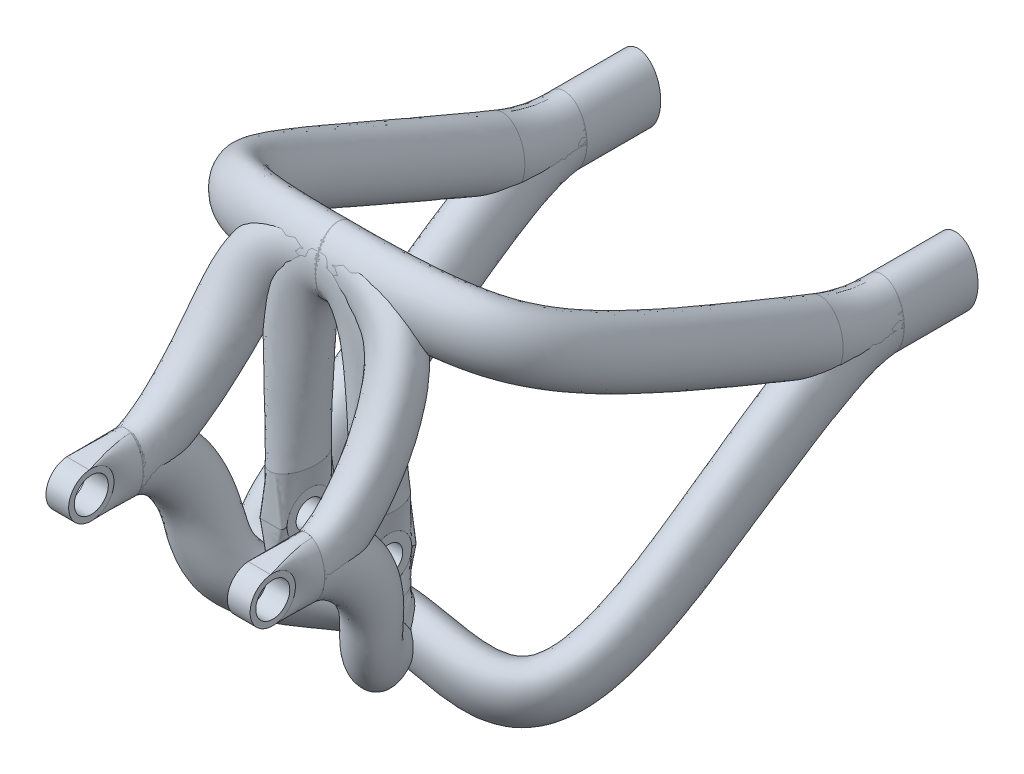
SolidWorks part; units mm, degrees
ref_plane "Płaszczyzna przednia" through (0, 0, 0) normal (0, 0, 1) x (1, 0, 0)
ref_plane "Płaszczyzna górna" through (0, 0, 0) normal (0, 1, 0) x (1, 0, 0)
ref_plane "Płaszczyzna prawa" through (0, 0, 0) normal (1, 0, 0) x (0, 0, -1)
sketch "Baza - płaszczyzna górna" plane through (0, 0, 0) normal (0, 1, 0) x (1, 0, 0)
  line L0 (0, 0) -> (0, 512) construction
  line L1 (117.5, 147.6) -> (-117.5, 147.6) construction
  line L2 (135, 0) -> (-135, 0) construction
  line L3 (-117.5, 512) -> (117.5, 512) construction
  line L4 (-117.5, 512) -> (-117.5, 147.6) construction
  line L5 (117.5, 512) -> (117.5, 147.6) construction
  line L6 (117.5, 186) -> (-117.5, 186) construction
  line L7 (135, 22.5) -> (135, -22.5) construction
  line L8 (-135, 22.5) -> (-135, -22.5) construction
  line L9 (117.5, 512) -> (125, 512) construction
  line L10 (125, 512) -> (125, 147.6) construction
  line L11 (125, 147.6) -> (117.5, 147.6) construction
  point P2 (0, 487)
  point P7 (0, 0)
  point P10 (0, 512)
  point P12 (0, 147.6)
  point P16 (135, 0)
  dimension "D1" = 512
  dimension "D2" = 147.6
  dimension "D3" = 270
  dimension "D4" = 235
  dimension "D5" = 326
  dimension "D6" = 45
  dimension "D7" = 25
  dimension "D8" = 125
sketch "Baza - płaszczyzna prawa" plane through (0, 0, 0) normal (1, 0, 0) x (0, 0, -1)
  line L0 (0, 0) -> (512, 0) construction
  line L1 (0, 0) -> (512, 0) construction
  line L2 (147.6, 0) -> (147.6, -66) construction
  arc A2 (440.6668, 297.4126) -> (440.6668, -297.4126) centre (487, 0) ccw
  dimension "D5" = 301
  dimension "D1" = 66
  dimension "D2" = 147.6
ref_plane "Powierzchnia styku z ramą" through (135, 0, 0) normal (1, 0, 0) x (0, 0, -1)
sketch "Szkic - insert - rama" plane through (135, 0, 0) normal (1, 0, 0) x (0, 0, -1)
  circle A0 centre (0, 0) radius 20
  circle A1 centre (0, 0) radius 15
  dimension "D1" = 40
  dimension "D2" = 30
ref_plane "Powierzchnia graniczna koła" through (125, 0, 0) normal (1, 0, 0) x (0, 0, -1)
ref_plane "Płaszczyzna pracy łańcucha" through (100, 0, 0) normal (1, 0, 0) x (0, 0, -1)
sketch "Łańcuch - baza" plane through (100, 0, 0) normal (1, 0, 0) x (0, 0, -1)
  line L0 (0, 0) -> (-72.4444, -19.4114) construction
  line L1 (0, 0) -> (512, 0) construction
  dimension "D1" = 75
  dimension "D2" = 165
sketch "Łańcuch - zarys" plane through (100, 0, 0) normal (1, 0, 0) x (0, 0, -1)
  line L0 (-75.0521, 2.4335) -> (503.4658, 71.4924)
  line L1 (-83.5151, 37.5222) -> (483.2736, 147.733)
  line L2 (-72.4444, -19.4114) -> (512, 0) construction
  line L3 (-79.7129, -76.9542) -> (493.1396, -149.3135)
  line L4 (-73.5969, -41.3812) -> (508.2284, -71.9011)
  circle A0 centre (-72.4444, -19.4114) radius 22
  circle A1 centre (512, 0) radius 72
  arc A2 (-83.5151, 37.5222) -> (-79.7129, -76.9542) centre (-72.4444, -19.4114) ccw
  arc A3 (493.1396, -149.3135) -> (483.2736, 147.733) centre (512, 0) ccw
  point P0 (-72.4444, -19.4114)
  point P2 (512, 0)
  dimension "D1" = 44
  dimension "D2" = 144
  dimension "D3" = 116
  dimension "D4" = 301
ref_axis "Oś tynego koła" through (-117.5, 0, -512) along (1, 0, 0)
ref_axis "Oś mocowania do ramy" through (135, 0, 0) along (-1, 0, 0)
ref_axis "Oś mocowania linkage" through (0, -66, -147.6) along (1, 0, 0)
sketch "Szkic - insert - linkage" plane through (0, 0, 0) normal (1, 0, 0) x (0, 0, -1)
  circle A0 centre (147.6, -66) radius 12
  circle A1 centre (147.6, -66) radius 20
  dimension "D1" = 40
  dimension "D2" = 24
extrude "Rama" add sketch "Szkic - insert - rama" against normal mid plane 20 from offset 55 offset against normal yes
extrude "Linkage" add sketch "Szkic - insert - linkage" along normal blind 20 from offset 25 separate body
sketch "Szkic - insert - tylne koło" plane through (125, 0, 0) normal (1, 0, 0) x (0, 0, -1)
  line L0 (487, 20) -> (552, 20)
  line L1 (512, 0) -> (147.6, 0) construction
  line L2 (487, -20) -> (552, -20)
  line L3 (537, 8) -> (487, 8)
  line L4 (537, -8) -> (487, -8)
  line L5 (552, -20) -> (552, 20)
  arc A1 (487, 8) -> (487, -8) centre (487, 0) ccw
  arc A2 (537, -8) -> (537, 8) centre (537, 0) ccw
  arc A3 (487, 20) -> (487, -20) centre (487, 0) ccw
  dimension "D1" = 40
  dimension "D3" = 8
  dimension "D2" = 65
  dimension "D4" = 487
  dimension "D5" = 537
extrude "Tylne koło" add sketch "Szkic - insert - tylne koło" along normal blind 15 separate body
sketch "Szkic otwór łańcuch" plane through (0, 0, 0) normal (0, 0, 1) x (1, 0, 0)
  line L3 (100, -130) -> (110, -130)
  line L13 (115, -125) -> (115, -45)
  line L14 (110, -40) -> (100, -40)
  line L15 (95, -45) -> (95, -125)
  arc A0 (100, -130) -> (95, -125) centre (100, -125) cw
  arc A1 (110, -130) -> (115, -125) centre (110, -125) ccw
  arc A2 (115, -45) -> (110, -40) centre (110, -45) ccw
  arc A3 (100, -40) -> (95, -45) centre (100, -45) ccw
  dimension "D1" = 5
  dimension "D2" = 95
  dimension "D3" = 20
  dimension "D4" = 40
  dimension "D5" = 90
ref_plane "Płaszczyzna1" through (0, 0, -552) normal (0, 0, 1) x (1, 0, 0)
sketch "Szkic1" plane through (0, 0, -552) normal (0, 0, 1) x (1, 0, 0)
  line L0 (125, -20) -> (125, 20) construction
  line L1 (125, -20) -> (125, 20) construction
  ellipse E0 centre (139.9071, 0) end of major axis (139.9071, -30) minor radius 20
  dimension "D1" = 40
  dimension "D2" = 60
ref_plane "Płaszczyzna2" through (0, 0, -487) normal (0, 0, 1) x (1, 0, 0)
sketch "Szkic2" plane through (0, 0, -487) normal (0, 0, 1) x (1, 0, 0)
  ellipse E0 centre (139.9071, 0) end of major axis (139.9071, -30) minor radius 20 construction
  ellipse E1 centre (139.9071, 0) end of major axis (139.9071, -30) minor radius 20
sketch3d "Szkic 3D1"
  line L0 (139.9071, 0, -487) -> (139.9071, 0, -552)
  line L2 (0, 0, -147.6) -> (0, 158.7201, -147.6) construction
  line L3 (119.3246, 140, -147.6) -> (-119.3246, 140, -147.6) construction
  line L4 (140.0724, 7.5182, -440.5114) -> (140.5573, 28.6822, -388.43) construction
  line L5 (139.9071, 0, -502.2142) -> (139.9071, 0, -471.7253) construction
  spline S0 degree 3 poles (0, 140, -147.6) (156.552, 140, -147.6) (142.3562, 107.1992, -195.2116) (140.1456, 10.7124, -432.651) knots 0 0 0 0 0.922837 0.922837 0.922837 0.922837
  spline S1 degree 3 poles (140.1456, 10.7124, -432.651) (139.9436, 1.8941, -454.3516) (139.9071, 0, -467.9444) (139.9071, 0, -487) knots 0.922837 0.922837 0.922837 0.922837 1 1 1 1
  dimension "D1" = 140
surface "Powierzchnia-Wyciągnięcie po ścieżce2"
sketch3d "Szkic 3D2"
  circle A0 centre (70, 0, 0) radius 20 construction
  circle A1 centre (90, 0, 0) radius 20 construction
  arc A2 (70, -19.9375, -1.5799) -> (70, 19.9231, 1.7525) centre (70, 0, 0) ccw
  arc A3 (90, -19.9465, -1.4615) -> (90, 19.9268, 1.7094) centre (90, 0, 0) ccw
  circle A4 centre (70, 0, 0) radius 20 construction
  circle A5 centre (90, 0, 0) radius 20 construction
  circle A6 centre (70, 0, 0) radius 20 construction
  circle A7 centre (90, 0, 0) radius 20 construction
  spline S0 degree 1 poles (70, 19.9231, 1.7525) (90, 19.9268, 1.7094) knots 0 0 1 1
  spline S1 degree 1 poles (70, -19.9375, -1.5799) (90, -19.9465, -1.4615) knots 0 0 1 1
  point P2 (90, 0, 0)
  point P5 (110, 0, 0)
  point P7 (90, 0, 0)
  point P9 (110, 0, 0)
  point P14 (90, 0, 0)
  point P17 (110, 0, 0)
  point P22 (90, 0, 0)
  point P25 (110, 0, 0)
ref_plane "Płaszczyzna3" through (0, 0, -40) normal (0, 0, 1) x (1, 0, 0)
sketch "Szkic3" plane through (0, 0, -40) normal (0, 0, 1) x (1, 0, 0)
  line L0 (70, -19.9375) -> (70, 20) construction
  line L1 (90, -19.9465) -> (90, 20) construction
  line L2 (70, -19.9375) -> (70, 20) construction
  line L3 (90, -19.9465) -> (90, 20) construction
  line L4 (90, -19.9465) -> (70, 19.9231) construction
  line L5 (70, -19.9375) -> (90, 19.9268) construction
  ellipse E0 centre (80, -0.0117) end of major axis (80, 25.8035) minor radius 15.7433
  spline S0 degree 3 poles (-1929.9876, -19.0343) (-589.9986, -19.6394) (749.9903, -20.2446) (2089.9792, -20.8497) knots -99.999378 -99.999378 -99.999378 -99.999378 100.998962 100.998962 100.998962 100.998962 only from (70, -19.9375) to (90, -19.9465) construction
  spline S1 degree 3 poles (-1929.9879, 19.5485) (-589.9987, 19.7995) (749.9904, 20.0504) (2089.9796, 20.3013) knots -99.999395 -99.999395 -99.999395 -99.999395 100.998979 100.998979 100.998979 100.998979 only from (70, 19.9231) to (90, 19.9268) construction
  spline S2 degree 3 poles (70, -19.9375) (76.6667, -19.9405) (83.3333, -19.9435) (90, -19.9465) knots 0 0 0 0 1 1 1 1 construction
  spline S3 degree 3 poles (70, 19.9231) (76.6667, 19.9243) (83.3333, 19.9256) (90, 19.9268) knots 0 0 0 0 1 1 1 1 construction
  point P2 (80, -0.0117)
surface "Powierzchnia-Wyciągnięcie po profilach1" end constraint normal to profile end tangent length 1
sketch3d "Szkic 3D3"
  line L0 (0, 110, -147.6) -> (0, 170, -147.6) construction
  line L1 (0, 140, -147.6) -> (0, 140, -167.6) construction
  line L2 (0, 140, -167.6) -> (0, 140, -127.6) construction
  spline S0 degree 3 poles (0, 110, -147.6) (0, 110, -107.6) (0, 170, -107.6) (0, 170, -147.6) (0, 170, -187.6) (0, 110, -187.6) (0, 110, -147.6) (0, 110, -107.6) (0, 170, -107.6) knots -0.5 0 0 0 0.5 0.5 0.5 1 1 1 1.5 1.5 1.5 weights 1 0.333333 0.333333 1 0.333333 0.333333 1 0.333333 0.333333 only from (0, 110, -147.6) to (0, 110, -147.6) construction
  spline S1 degree 3 poles (0, 110, -147.6) (0, 110, -107.6) (0, 170, -107.6) (0, 170, -147.6) (0, 170, -187.6) (0, 110, -187.6) (0, 110, -147.6) (0, 110, -107.6) (0, 170, -107.6) knots -0.5 0 0 0 0.5 0.5 0.5 1 1 1 1.5 1.5 1.5 weights 1 0.333333 0.333333 1 0.333333 0.333333 1 0.333333 0.333333 only from (0, 110, -147.6) to (0, 110, -147.6)
sketch3d "Szkic 3D4"
  line L0 (-17.1198, 140, -147.6) -> (35.4624, 140, -147.6) construction
  line L1 (80, -0.0117, -59.3206) -> (80, -0.0117, -20.3916) construction
  spline S0 degree 3 poles (80, -0.0117, -40) (80, -0.0117, -64.3306) (75.1674, 69.9941, -132.2808) (59.2924, 140, -147.6) (0, 140, -147.6) knots 0 0 0 0 0.462724 1 1 1 1
surface "Powierzchnia-Wyciągnięcie po profilach3"
sketch "Szkic3<4>" plane through (0, 0, -40) normal (0, 0, 1) x (1, 0, 0) same geometry as "Szkic3"
sketch "Szkic4" plane through (0, 0, 0) normal (1, 0, 0) x (0, 0, -1)
  line L0 (179.3553, 0) -> (179.3553, -173.0425) construction
  line L1 (0, 0) -> (512, 0) construction
  line L2 (147.6, -66) -> (179.3553, -137.0609) construction
  ellipse E0 centre (179.3553, -137.0609) end of major axis (191.595, -164.4505) minor radius 20
  dimension "D1" = 60
  dimension "D2" = 40
sketch3d "Szkic 3D5"
  line L0 (139.9071, 0, -531.3863) -> (139.9071, 0, -439.8518) construction
  line L1 (18.4345, -137.0609, -179.3553) -> (-25.1846, -137.0609, -179.3553) construction
  spline S0 degree 3 poles (0, -137.0609, -179.3553) (69.0829, -137.0609, -179.3553) (118.485, -183.6678, -172.5611) (141.5721, -114.7186, -307.0519) (139.9071, 0, -439.2631) (139.9071, 0, -487) knots 0 0 0 0 0.519742 0.619742 1 1 1 1
surface "Powierzchnia-Wyciągnięcie po profilach4"
sketch3d "Szkic 3D6"
  line L0 (0, -164.0837, -192.3511) -> (0, -109.7304, -166.9846) construction
  line L1 (0, -109.7304, -166.9846) -> (0, -136.907, -179.6678) construction
  line L2 (-23.1985, -136.907, -179.6678) -> (23.1985, -136.907, -179.6678) construction
  line L3 (80, -0.0117, -41.42) -> (80, -0.0117, -5.881) construction
  line L4 (0, -145.5132, -161.2273) -> (0, -136.907, -179.6678) construction
  line L5 (0, -136.907, -179.6678) -> (0, -128.5954, -197.4772) construction
  spline S0 degree 3 poles (0, -164.3404, -191.8618) (0, -163.8269, -192.8403) (0, -163.2578, -193.7805) (0, -162.2463, -195.0746) (0, -161.0864, -196.2514) (0, -153.2931, -202.5999) (0, -139.6894, -202.8229) (0, -112.8437, -189.9122) (0, -104.9038, -176.1447) (0, -115.1727, -156.5743) (0, -131.4497, -154.4531) (0, -158.2953, -167.3638) (0, -166.2299, -177.9451) (0, -165.5626, -187.7206) (0, -165.269, -189.3139) (0, -164.7884, -190.8634) (0, -164.3404, -191.8618) (0, -163.8269, -192.8403) (0, -163.2578, -193.7805) knots -0.025 -0.0125 0 0 0.0125 0.025 0.0375 0.05 0.25 0.25 0.5 0.5 0.75 0.75 0.95 0.9625 0.975 0.9875 1 1 1.0125 1.025 1.0375 only from (0, -164.0837, -192.3511) to (0, -164.0837, -192.3511) construction
  spline S1 degree 3 poles (0, -164.3404, -191.8618) (0, -163.8269, -192.8403) (0, -163.2578, -193.7805) (0, -162.2463, -195.0746) (0, -161.0864, -196.2514) (0, -153.2931, -202.5999) (0, -139.6894, -202.8229) (0, -112.8437, -189.9122) (0, -104.9038, -176.1447) (0, -115.1727, -156.5743) (0, -131.4497, -154.4531) (0, -158.2953, -167.3638) (0, -166.2299, -177.9451) (0, -165.5626, -187.7206) (0, -165.269, -189.3139) (0, -164.7884, -190.8634) (0, -164.3404, -191.8618) (0, -163.8269, -192.8403) (0, -163.2578, -193.7805) knots -0.025 -0.0125 0 0 0.0125 0.025 0.0375 0.05 0.25 0.25 0.5 0.5 0.75 0.75 0.95 0.9625 0.975 0.9875 1 1 1.0125 1.025 1.0375 only from (0, -164.0837, -192.3511) to (0, -164.0837, -192.3511)
  spline S2 degree 3 poles (80, -0.0117, -40) (80, -0.0117, -62.2654) (82.1415, -27.0836, -100.0728) (62.3511, -135.8151, -110.0435) (25.5109, -136.907, -179.6678) (0, -136.907, -179.6678) knots 0 0 0 0 0.446189 0.546189 1 1 1 1
surface "Powierzchnia-Wyciągnięcie po profilach5"
sketch "Szkic3<6>" plane through (0, 0, -40) normal (0, 0, 1) x (1, 0, 0) same geometry as "Szkic3"
sketch3d "Szkic 3D7"
  line L0 (45, -66, -170.6) -> (45, -66, -169.5089)
  line L1 (25, -66, -193.7452) -> (25, -66, -101.6536) construction
  line L2 (45, -66, -125.6911) -> (45, -66, -124.6)
  line L3 (43, -66, -172.6) -> (27, -66, -172.6)
  line L4 (25, -66, -170.6) -> (25, -66, -169.5089)
  line L5 (43, -66, -122.6) -> (27, -66, -122.6)
  line L6 (25, -66, -125.6911) -> (25, -66, -124.6)
  line L7 (43, -66, -172.6) -> (27, -66, -122.6) construction
  line L8 (43, -66, -122.6) -> (27, -66, -172.6) construction
  line L9 (45, -46, -147.6) -> (25, -46, -147.6) construction
  circle A0 centre (45, -66, -147.6) radius 20 construction
  circle A1 centre (25, -66, -147.6) radius 20 construction
  arc A2 (45, -64.1818, -167.5172) -> (45, -64.1818, -127.6828) centre (45, -66, -147.6) ccw
  arc A3 (25, -64.1818, -167.5172) -> (25, -64.1818, -127.6828) centre (25, -66, -147.6) ccw
  arc A4 (27, -66, -122.6) -> (25, -66, -124.6) centre (27, -66, -124.6) ccw
  arc A5 (43, -66, -122.6) -> (45, -66, -124.6) centre (43, -66, -124.6) ccw
  arc A6 (45, -66, -125.6911) -> (45, -64.1818, -127.6828) centre (45, -64, -125.6911) ccw
  arc A7 (25, -66, -125.6911) -> (25, -64.1818, -127.6828) centre (25, -64, -125.6911) ccw
  arc A8 (45, -64.1818, -167.5172) -> (45, -66, -169.5089) centre (45, -64, -169.5089) ccw
  arc A9 (45, -66, -170.6) -> (43, -66, -172.6) centre (43, -66, -170.6) ccw
  arc A10 (27, -66, -172.6) -> (25, -66, -170.6) centre (27, -66, -170.6) ccw
  arc A11 (25, -64.1818, -167.5172) -> (25, -66, -169.5089) centre (25, -64, -169.5089) ccw
  point P6 (65, -66, -147.6)
  point P9 (45, -66, -147.6)
  point P11 (65, -66, -147.6)
  point P13 (45, -66, -147.6)
  point P20 (25, -66, -122.6)
  point P21 (27, -68, -124.6)
  point P24 (45, -66, -122.6)
  point P25 (43, -64, -124.6)
  point P28 (47, -64, -125.6911)
  point P31 (27, -64, -125.6911)
  point P34 (47, -64, -169.5089)
  point P37 (45, -66, -172.6)
  point P38 (43, -64, -170.6)
  point P41 (25, -66, -172.6)
  point P42 (27, -64, -170.6)
  point P45 (27, -64, -169.5089)
  point P48 (35, -46, -147.6)
  dimension "D2" = 2
  dimension "D1" = 50
ref_plane "Płaszczyzna4" through (0, -66, 0) normal (0, 1, 0) x (1, 0, 0)
sketch3d "Szkic 3D8"
  line L0 (43, -66, -172.6) -> (27, -66, -172.6) construction
  line L1 (45, -66, -170.6) -> (45, -66, -169.5089) construction
  line L2 (25, -66, -170.6) -> (25, -66, -169.5089) construction
  line L3 (25, -66, -125.6911) -> (25, -66, -124.6) construction
  line L4 (43, -66, -122.6) -> (27, -66, -122.6) construction
  line L5 (45, -66, -125.6911) -> (45, -66, -124.6) construction
  line L6 (43, -66, -172.6) -> (27, -66, -172.6)
  line L7 (45, -66, -170.6) -> (45, -66, -169.5089)
  line L8 (25, -66, -170.6) -> (25, -66, -169.5089)
  line L9 (25, -66, -125.6911) -> (25, -66, -124.6)
  line L10 (43, -66, -122.6) -> (27, -66, -122.6)
  line L11 (45, -66, -125.6911) -> (45, -66, -124.6)
  arc A0 (25, -64.1818, -167.5172) -> (25, -64.1818, -127.6828) centre (25, -66, -147.6) ccw construction
  arc A4 (25, -64.1818, -167.5172) -> (25, -66, -169.5089) centre (25, -64, -169.5089) ccw construction
  arc A5 (25, -66, -125.6911) -> (25, -64.1818, -127.6828) centre (25, -64, -125.6911) ccw construction
  arc A8 (45, -66, -125.6911) -> (45, -64.1818, -127.6828) centre (45, -64, -125.6911) ccw construction
  arc A10 (45, -64.1818, -167.5172) -> (45, -66, -169.5089) centre (45, -64, -169.5089) ccw construction
  arc A22 (45, -67.8182, -127.6828) -> (45, -67.8182, -167.5172) centre (45, -66, -147.6) cw
  arc A23 (45, -67.8182, -127.6828) -> (45, -66, -125.6911) centre (45, -68, -125.6911) cw
  arc A24 (45, -66, -124.6) -> (43, -66, -122.6) centre (43, -66, -124.6) cw
  arc A25 (25, -66, -124.6) -> (27, -66, -122.6) centre (27, -66, -124.6) cw
  arc A29 (25, -66, -170.6) -> (27, -66, -172.6) centre (27, -66, -170.6) cw
  arc A30 (43, -66, -172.6) -> (45, -66, -170.6) centre (43, -66, -170.6) cw
  arc A31 (25, -67.8182, -127.6828) -> (25, -67.8182, -167.5172) centre (25, -66, -147.6) cw
  arc A32 (25, -67.8182, -127.6828) -> (25, -66, -125.6911) centre (25, -68, -125.6911) cw
  arc A33 (45, -66, -169.5089) -> (45, -67.8182, -167.5172) centre (45, -68, -169.5089) cw
  arc A34 (25, -66, -169.5089) -> (25, -67.8182, -167.5172) centre (25, -68, -169.5089) cw
  point P3 (45, -66, -147.6)
  point P4 (45, -66, -147.6)
  point P22 (27, -64, -169.5089)
  point P26 (27, -64, -125.6911)
  point P34 (65, -66, -147.6)
  point P44 (47, -64, -125.6911)
  point P52 (47, -64, -169.5089)
  point P53 (47, -68, -125.6911)
  point P54 (43, -68, -124.6)
  point P55 (27, -64, -124.6)
  point P62 (27, -68, -170.6)
  point P63 (43, -68, -170.6)
  point P64 (27, -68, -125.6911)
  point P65 (47, -68, -169.5089)
  point P66 (27, -68, -169.5089)
sketch3d "Szkic 3D9"
  line L0 (-25.5478, 140, -147.6) -> (25.7777, 140, -147.6) construction
  line L1 (35, -36.3172, -147.6) -> (35, -61.4967, -147.6) construction
  spline S0 degree 3 poles (35, -46, -147.6) (35, -30.2628, -147.6) (33.494, 35.7862, -147.6) (34.6214, 140, -147.6) (0, 140, -147.6) knots 0 0 0 0 0.49153 1 1 1 1
ref_plane "Płaszczyzna7" through (0, -26, 0) normal (0, 1, 0) x (1, 0, 0)
sketch "Szkic7" plane through (0, -26, 0) normal (0, 1, 0) x (1, 0, 0)
  line L1 (35, 147.6) -> (0, 147.6) construction
  ellipse E0 centre (35, 147.6) end of major axis (34.6851, 172.6) minor radius 15.0012
  point P0 (35, 147.6)
  dimension "D1" = 50
  dimension "D2" = 30
surface "Powierzchnia-Wyciągnięcie po profilach6"
surface "Powierzchnia-Wyciągnięcie po profilach7"
sketch3d "Szkic 3D3<4>" same geometry as "Szkic 3D3"
ref_plane "Płaszczyzna8" through (0, -96, 0) normal (0, 1, 0) x (1, 0, 0)
sketch "Szkic8" plane through (0, -96, 0) normal (0, 1, 0) x (1, 0, 0)
  line L0 (43, 172.6) -> (27, 122.6) construction
  ellipse E0 centre (35, 147.6) end of major axis (35, 172.6) minor radius 15
  point P0 (35, 147.6)
  dimension "D1" = 50
  dimension "D2" = 30
surface "Powierzchnia-Wyciągnięcie po profilach8"
sketch3d "Szkic 3D10"
  line L0 (35, -71.3664, -147.6) -> (35, -120.6336, -147.6) construction
  line L1 (19.3357, -136.907, -179.6678) -> (-29.5587, -136.907, -179.6678) construction
  spline S0 degree 3 poles (0, -136.907, -179.6678) (35.6844, -136.907, -179.6678) (35, -124.5646, -147.6) (35, -96, -147.6) knots 0 0 0 0 1 1 1 1
surface "Powierzchnia-Wyciągnięcie po profilach9"
mirror "Lustro3" about plane through (0, 0, 0) normal (1, 0, 0) of bodies 148 146 143 150 152 151 149 153 145 103 104
